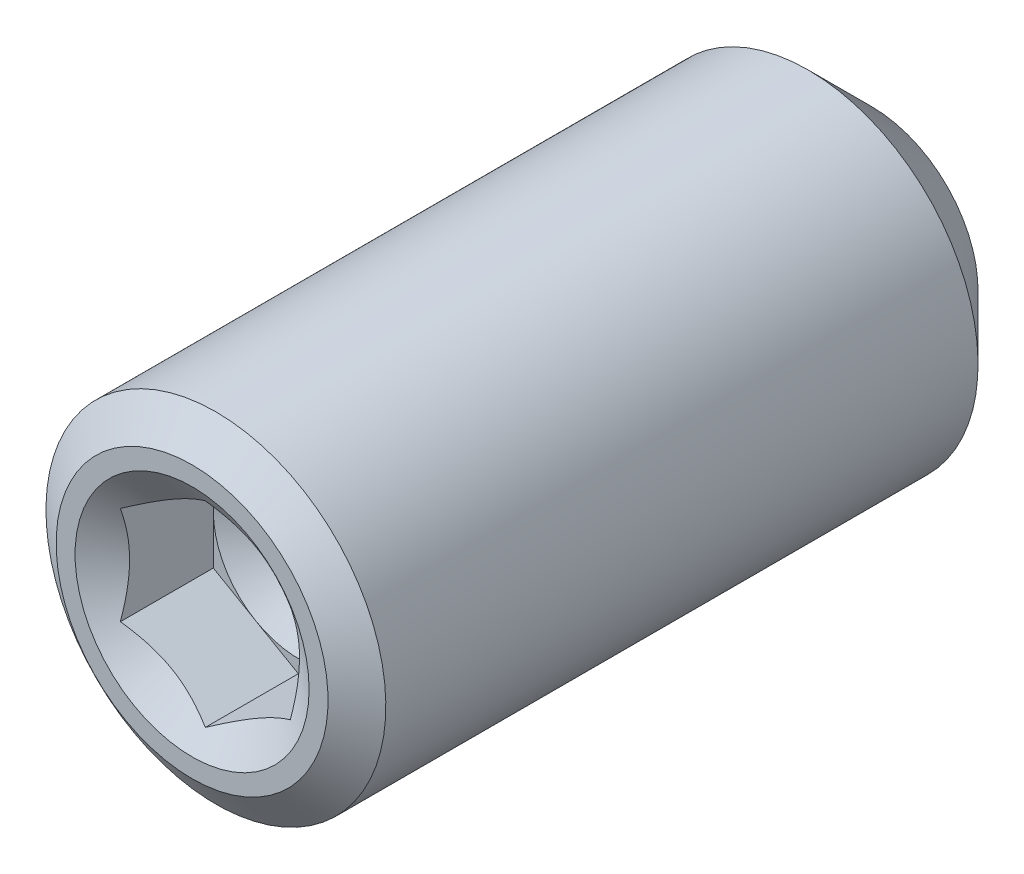
SolidWorks part; units mm, degrees
ref_plane "Front Plane" through (0, 0, 0) normal (0, 0, 1) x (1, 0, 0)
ref_plane "Top Plane" through (0, 0, 0) normal (0, 1, 0) x (1, 0, 0)
ref_plane "Right Plane" through (0, 0, 0) normal (1, 0, 0) x (0, 0, -1)
sketch "Sketch1" plane through (0, 0, 0) normal (1, 0, 0) x (0, 0, -1)
  line L0 (-2.7808, 0) -> (-2.7808, 1.2)
  line L1 (-2.7808, 1.2) -> (-2.5708, 1.5)
  line L2 (-2.5708, 1.5) -> (2.6567, 1.5)
  line L3 (2.6567, 1.5) -> (3.2192, 0.9375)
  line L5 (2.7808, 0) -> (-2.7808, 0)
  line L6 (2.7808, 0) -> (3.2192, 0) construction
  line L7 (3.2192, 0) -> (3.2192, 0.9375) construction
  line L8 (3.2192, -0.9375) -> (2.7808, 0) construction
  line L9 (-2.5708, -1.5) -> (2.6567, -1.5) construction
  line L10 (0, 0) -> (0, -0.5) construction
  line L11 (2.7808, 0) -> (3.112, 0.5512)
  line L12 (2.7808, 0) -> (3.112, -0.5512) construction
  arc A0 (3.112, 0.5512) -> (3.2192, 0.9375) centre (2.4692, 0.9375) ccw
  arc A1 (3.112, -0.5512) -> (3.2192, -0.9375) centre (2.4692, -0.9375) cw construction
  point P11 (-2.7808, 1.5)
  point P12 (1.4692, -1.5)
  point P13 (-1.5308, -1.5)
  point P14 (3.2192, 1.5)
  dimension "D5" = 0.75
  dimension "Thread Size" = 3
  dimension "Length" = 6
  dimension "D3" = 35
  dimension "D6" = 45
  dimension "D7" = 2.4
  dimension "Thread Pitch" = 0.5
  dimension "D2" = 1.25
  dimension "D4" = 59
  dimension "D8" = 1.875
  dimension "D1" = 1.75
sketch "Sketch2" plane through (0, 0, 0) normal (0, 0, 1) x (1, 0, 0)
  line L1 (0.75, 0.433) -> (0, 0.866) construction
  line L2 (0, 0.866) -> (-0.75, 0.433) construction
  line L3 (-0.75, 0.433) -> (-0.75, -0.433) construction
  line L4 (-0.75, -0.433) -> (0, -0.866) construction
  line L5 (0, -0.866) -> (0.75, -0.433) construction
  line L6 (0.75, -0.433) -> (0.75, 0.433) construction
  circle A0 centre (0, 0) radius 0.75 construction
  circle A1 centre (0, 0) radius 1.5 construction
  dimension "Drive Size" = 1.5
sketch "Sketch4" plane through (0, 0, 0) normal (1, 0, 0) x (0, 0, -1)
  line L0 (2.7808, 0) -> (3.112, 0.5512) construction
  line L1 (-2.5708, 1.5) -> (2.6567, 1.5) construction
  line L2 (-2.7808, 0) -> (-2.7808, 1.2) construction
  line L3 (2.7808, 0) -> (-2.7808, 0) construction
  line L4 (2.7808, 0) -> (3.112, 0.5512)
  line L5 (2.6567, 1.5) -> (3.2192, 0.9375) construction
  line L6 (2.6567, 1.5) -> (3.2192, 0.9375)
  line L8 (2.7808, 0) -> (-2.7808, 0)
  line L9 (-2.7808, 0) -> (-2.7808, 1.2)
  line L10 (-2.5708, 1.5) -> (2.6567, 1.5)
  line L11 (-2.7808, 1.2) -> (-2.5708, 1.5) construction
  line L12 (-2.7808, 1.2) -> (-2.5708, 1.5)
  arc A0 (3.112, 0.5512) -> (3.2192, 0.9375) centre (2.4692, 0.9375) ccw construction
  arc A1 (3.112, 0.5512) -> (3.2192, 0.9375) centre (2.4692, 0.9375) ccw
revolve "Revolve1" add sketch "Sketch4" angle 360 about L8
sketch "Sketch6" plane through (0, 0, 2.7808) normal (0, 0, 1) x (1, 0, 0)
  line L1 (0.75, 0.433) -> (0, 0.866)
  line L2 (0, 0.866) -> (-0.75, 0.433)
  line L3 (-0.75, 0.433) -> (-0.75, -0.433)
  line L4 (-0.75, -0.433) -> (0, -0.866)
  line L5 (0, -0.866) -> (0.75, -0.433)
  line L6 (0.75, -0.433) -> (0.75, 0.433)
  circle A0 centre (0, 0) radius 0.75 construction
  dimension "D1" = 1.5
extrude "Cut-Extrude3" cut sketch "Sketch6" against normal blind 0.9375
sketch "Sketch7" plane through (0, 0, 2.7808) normal (0, 0, 1) x (1, 0, 0)
  line L0 (0, 0.866) -> (0, 1.2) construction
  circle A0 centre (0, 0) radius 1.033
  circle A2 centre (0, 0) radius 1.2 construction
  point P6 (0, 1.033)
  point P10 (0, 1.033)
extrude "Cut-Extrude4" cut sketch "Sketch7" against normal through all draft 55
sketch "Sketch8" plane through (0, 0, 1.8433) normal (0, 0, 1) x (1, 0, 0)
  circle A0 centre (0, 0) radius 0.75 construction
  circle A1 centre (0, 0) radius 0.75
extrude "Cut-Extrude5" cut sketch "Sketch8" against normal through all draft 60
ref_plane "Plane1" [suppressed] through (0, 0, -3.2192) normal (0, 0, 1) x (1, 0, 0)
sketch "Sketch9" [suppressed] plane through (0, 0, -3.2192) normal (0, 0, 1) x (1, 0, 0)
  circle A0 centre (0, 0) radius 1.5 construction
  circle A1 centre (0, 0) radius 1.5
curve "Helix/Spiral1" [suppressed] pitch 0.5 height 6.5 turns 13
sketch "Sketch10" [suppressed] plane through (0, 0, 0) normal (1, 0, 0) x (0, 0, -1)
  line L0 (3.2192, 1.5) -> (3.6567, 1.5)
  line L1 (3.6567, 1.5) -> (3.4692, 1.1752)
  line L2 (3.4067, 1.1752) -> (3.2192, 1.5)
  line L3 (3.4067, 1.1752) -> (3.4692, 1.1752)
  line L4 (3.4379, 1.1752) -> (3.4379, 1.5) construction
  line L5 (3.3129, 1.3376) -> (3.5629, 1.3376) construction
  point P10 (3.4379, 1.3376)
  dimension "D1" = 60
  dimension "D2" = 0.0625
  dimension "D3" = 0.25
sweep "Cut-Sweep1" [suppressed] cut profiles "Sketch10" path "Helix/Spiral1"
equation "\"D7@Sketch1\" = \"Thread Size@Sketch1\" * .8"
equation "\"D3\"= \"Length@Sketch1\" + \"Thread Pitch@Sketch1\""
equation "\"D4\"= \"Thread Pitch@Sketch1\""
equation "\"D1@Sketch6\"=\"Drive Size@Sketch2\""
equation "\"D1@Cut-Extrude3\"=\"Drive Size@Sketch2\"*.625"
equation "\"D3@Helix/Spiral1\"=\"Length@Sketch1\"+\"Thread Pitch@Sketch1\""
equation "\"D4@Helix/Spiral1\"=\"Thread Pitch@Sketch1\""
equation "\"D2@Sketch10\"=\"Thread Pitch@Sketch1\"/8"
equation "\"D3@Sketch10\"=\"Thread Pitch@Sketch1\"/2"
equation "\"D2@Sketch1\"=\"Thread Pitch@Sketch1\"*2.5"
equation "\"D5@Sketch1\"=\"Thread Size@Sketch1\"*.25"
equation "\"D8@Sketch1\"=\"Thread Size@Sketch1\"*.625"
equation "\"D1@Sketch1\"=\"Thread Pitch@Sketch1\"*3.5"
